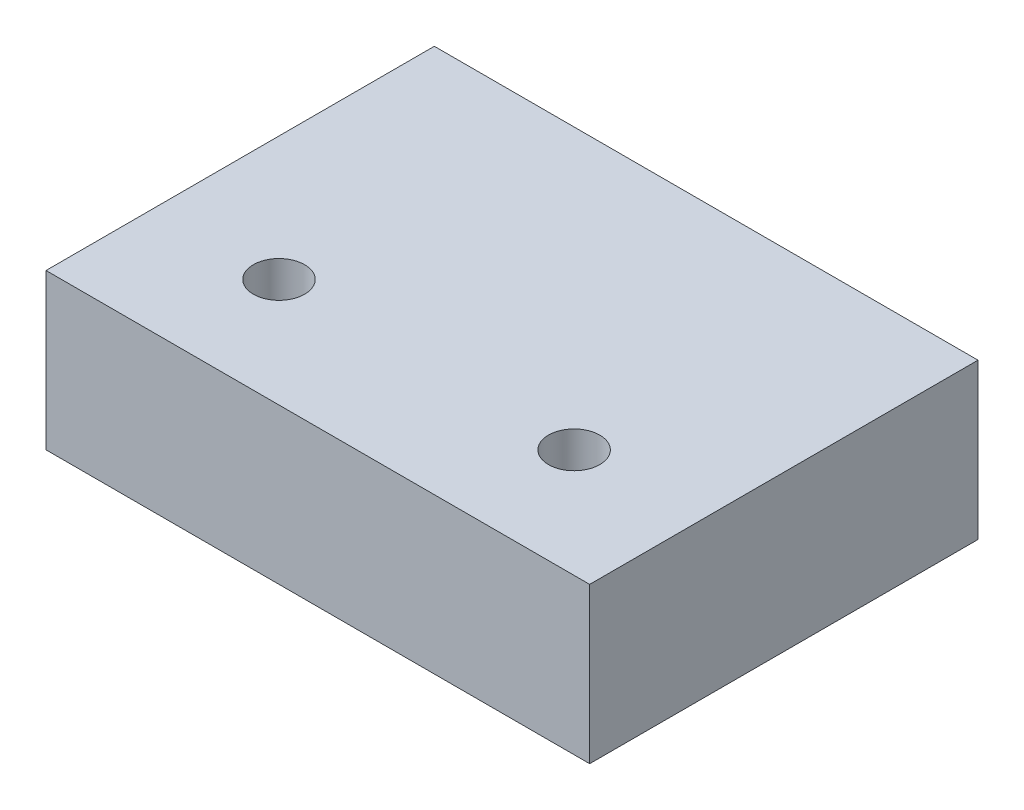
SolidWorks part; units mm, degrees
ref_plane "Plan de face" through (0, 0, 0) normal (0, 0, 1) x (1, 0, 0)
ref_plane "Plan de dessus" through (0, 0, 0) normal (0, 1, 0) x (1, 0, 0)
ref_plane "Plan de droite" through (0, 0, 0) normal (1, 0, 0) x (0, 0, -1)
sketch "Esquisse1" plane through (0, 0, 0) normal (0, 1, 0) x (1, 0, 0)
  line L1 (-17.5, -12.5) -> (17.5, -12.5)
  line L2 (-17.5, -12.5) -> (-17.5, 12.5)
  line L3 (-17.5, 12.5) -> (17.5, 12.5)
  line L4 (17.5, -12.5) -> (17.5, 12.5)
  line L5 (-17.5, -12.5) -> (17.5, 12.5) construction
  line L6 (-17.5, 12.5) -> (17.5, -12.5) construction
  point P0 (0, 0)
  dimension "D1" = 35
  dimension "D2" = 25
extrude "Boss.-Extru.1" add sketch "Esquisse1" along normal blind 10
sketch "Esquisse2" plane through (0, 10, 0) normal (0, 1, 0) x (1, 0, 0)
  line L0 (-17.5, -5.5) -> (17.5, -5.5) construction
  line L1 (-17.5, 12.5) -> (-17.5, -12.5) construction
  line L2 (17.5, -12.5) -> (17.5, 12.5) construction
  line L3 (-17.5, -12.5) -> (17.5, -12.5) construction
  line L4 (0, 0) -> (0, -5.5) construction
  circle A0 centre (9.5, -5.5) radius 1.65
  circle A1 centre (-9.5, -5.5) radius 1.65
  dimension "D2" = 3.3
  dimension "D3" = 8
  dimension "D1" = 7
extrude "Enlèv. mat.-Extru.1" cut sketch "Esquisse2" against normal blind 10
ref_axis "Axe1" through (9.5, 0, 5.5) along (0, 1, 0)
ref_axis "Axe2" through (-9.5, 0, 5.5) along (0, 1, 0)
